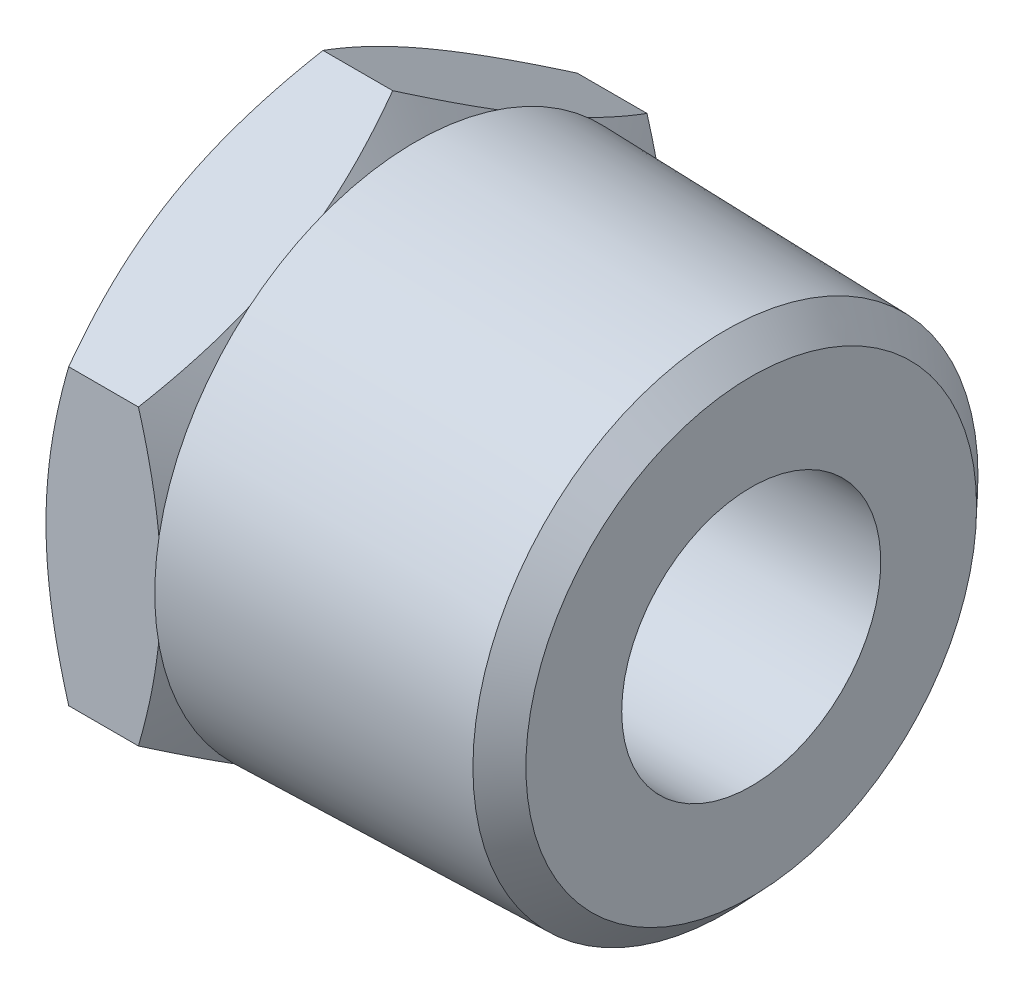
SolidWorks part; units mm, degrees
ref_plane "Front Plane" through (0, 0, 0) normal (0, 0, 1) x (1, 0, 0)
ref_plane "Top Plane" through (0, 0, 0) normal (0, 1, 0) x (1, 0, 0)
ref_plane "Right Plane" through (0, 0, 0) normal (1, 0, 0) x (0, 0, -1)
sketch "Sketch1" plane through (0, 0, 0) normal (0, 0, 1) x (1, 0, 0)
  line L0 (-11.938, 0) -> (11.938, 0) construction
  line L1 (-11.938, 13.462) -> (-11.938, -13.462) construction
  line L2 (11.938, 13.335) -> (11.938, -13.335) construction
  line L3 (-5.842, 6.858) -> (-5.842, -6.858) construction
  line L4 (11.938, -13.335) -> (-11.938, -13.9602) construction
  point P7 (-8.2169, 0)
  point P8 (-5.842, 0)
  point P11 (4.6809, -13.525)
  dimension "Male Pipe OD" = 26.67
  dimension "Hex" = 26.924
  dimension "Male TE" = 20.1549
  dimension "Female TE" = 6.096
  dimension "A" = 23.876
  dimension "Female Pipe OD" = 13.716
  dimension "D1" = 1.5
  dimension "D2" = 7.2571
ref_plane "Plane1" through (11.938, 0, 0) normal (1, 0, 0) x (0, 0, -1)
sketch "Sketch2" plane through (11.938, 0, 0) normal (1, 0, 0) x (0, 0, -1)
  circle A0 centre (0, 0) radius 13.335
extrude "Extrude1" add sketch "Sketch2" against normal up to vertex (17.78 mm away) draft 1.5 up to point (-5.842, 0, 0) draft outward yes
sketch "Sketch3" plane through (11.938, 0, 0) normal (1, 0, 0) x (0, 0, -1)
  circle A0 centre (0, 0) radius 13.335 construction
  circle A1 centre (0, 0) radius 13.335
curve "Helix/Spiral1" parameters "Male pitch"=1.8143
chamfer "Chamfer1" distance 1.3662 angle 45 1 edges at (11.938, 0, -13.335) first distance on face at (-5.842, 0, -13.8006)
sketch "Sketch4" plane through (0, 0, 0) normal (0, 0, 1) x (1, 0, 0)
  line L0 (11.1443, 13.335) -> (11.8246, 12.1566)
  line L1 (11.8246, 12.1566) -> (12.0514, 12.1566)
  line L2 (12.0514, 12.1566) -> (12.7317, 13.335)
  line L3 (11.1443, 13.335) -> (12.7317, 13.335) construction
  line L4 (11.938, 12.1566) -> (11.938, 13.335) construction
  line L5 (11.4844, 12.7458) -> (12.3916, 12.7458) construction
  line L6 (12.7317, 13.335) -> (10.9643, 13.6466)
  line L7 (11.1443, 13.335) -> (10.9643, 13.6466)
  dimension "D1" = 10
  dimension "D2" = 60
  dimension "D3" = 0.2268
  dimension "D4" = 0.9071
sweep "Cut-Sweep1" [suppressed] cut profiles "Sketch4" path "Helix/Spiral1"
sketch "Sketch5" plane through (-5.842, 0, 0) normal (-1, 0, 0) x (0, 0, 1)
  line L1 (0, 15.5446) -> (-13.462, 7.7723)
  line L2 (-13.462, 7.7723) -> (-13.462, -7.7723)
  line L3 (-13.462, -7.7723) -> (0, -15.5446)
  line L4 (0, -15.5446) -> (13.462, -7.7723)
  line L5 (13.462, -7.7723) -> (13.462, 7.7723)
  line L6 (13.462, 7.7723) -> (0, 15.5446)
  circle A0 centre (0, 0) radius 13.462 construction
  dimension "D1" = 26.924
extrude "Extrude2" add sketch "Sketch5" along normal up to vertex (6.096 mm away) up to point (-11.938, 0, 0)
ref_plane "Plane2" through (-5.842, 0, 0) normal (1, 0, 0) x (0, 0, -1)
sketch "Sketch6" plane through (-5.842, 0, 0) normal (1, 0, 0) x (0, 0, -1)
  circle A0 centre (0, 0) radius 6.858
extrude "Cut-Extrude1" cut sketch "Sketch6" against normal through all draft 1.5 draft outward yes
sketch "Sketch7" plane through (-5.842, 0, 0) normal (-1, 0, 0) x (0, 0, 1)
  circle A1 centre (0, 0) radius 6.858
  circle A2 centre (0, 0) radius 6.858
  dimension "D1" = 0
curve "Helix/Spiral2" parameters "Female Pitch"=1.4111
sketch "Sketch9" plane through (-11.938, 0, 0) normal (-1, 0, 0) x (0, 0, 1)
  circle A0 centre (0, 0) radius 7.0176 construction
  circle A1 centre (0, 0) radius 7.0176
sketch "Sketch8" plane through (0, 0, 0) normal (0, 0, 1) x (1, 0, 0)
  line L0 (-6.4594, 6.858) -> (-5.2246, 6.858) construction
  line L1 (-5.2246, 6.858) -> (-5.7538, 5.9415)
  line L2 (-5.7538, 5.9415) -> (-5.9302, 5.9415)
  line L3 (-5.9302, 5.9415) -> (-6.4594, 6.858)
  line L4 (-5.2246, 6.858) -> (-6.5993, 7.1004)
  line L5 (-6.4594, 6.858) -> (-6.5993, 7.1004)
  line L6 (-5.842, 5.9415) -> (-5.842, 6.858) construction
  line L7 (-6.1948, 6.3997) -> (-5.4892, 6.3997) construction
  dimension "D1" = 10
  dimension "D2" = 60
  dimension "D3" = 0.1764
  dimension "D4" = 0.7056
sweep "Sweep1" [suppressed] add profiles "Sketch8" path "Helix/Spiral2"
sketch "Sketch10" plane through (-11.938, 0, 0) normal (-1, 0, 0) x (0, 0, 1)
  line L3 (13.462, 7.7723) -> (0, 15.5446)
  line L4 (13.462, 7.7723) -> (0, 15.5446)
  line L5 (0, 15.5446) -> (-13.462, 7.7723)
  line L6 (0, 15.5446) -> (-13.462, 7.7723)
  line L10 (0, -15.5446) -> (13.462, -7.7723)
  line L11 (-13.462, 7.7723) -> (-13.462, -7.7723)
  line L12 (-13.462, 7.7723) -> (-13.462, -7.7723)
  line L13 (-13.462, -7.7723) -> (0, -15.5446)
  line L14 (-13.462, -7.7723) -> (0, -15.5446)
  line L15 (13.462, -7.7723) -> (13.462, 7.7723)
  line L16 (0, -15.5446) -> (13.462, -7.7723)
  line L17 (13.462, -7.7723) -> (13.462, 7.7723)
  dimension "D1" = 0
extrude "Cut-Extrude3" [suppressed] cut sketch "Sketch10" along normal through all
extrude "Cut-Extrude4" cut sketch "Sketch9" against normal through all draft 45
sketch "Sketch11" [suppressed] plane through (-5.842, 0, 0) normal (-1, 0, 0) x (0, 0, 1)
  circle A0 centre (0, 0) radius 5.9415
extrude "Cut-Extrude5" [suppressed] cut sketch "Sketch11" against normal through all
sketch "Sketch12" plane through (-11.938, 0, 0) normal (-1, 0, 0) x (0, 0, 1)
  circle A0 centre (0, 0) radius 13.462 construction
  circle A1 centre (0, 0) radius 13.462
extrude "Cut-Extrude6" cut sketch "Sketch12" against normal through all draft 60 flip side to cut
sketch "Sketch13" plane through (-5.842, 0, 0) normal (1, 0, 0) x (0, 0, -1)
  circle A1 centre (0, 0) radius 13.462
  circle A2 centre (0, 0) radius 13.462
  dimension "D1" = 0
extrude "Cut-Extrude7" cut sketch "Sketch13" against normal through all draft 60 flip side to cut
sketch "Sketch14" [suppressed] plane through (-11.938, 0, 0) normal (1, 0, 0) x (0, 0, -1)
  line L0 (0, 0) -> (4.2012, 4.2012) construction
  line L1 (0, 0) -> (5.9415, 0) construction
  circle A0 centre (0, 0) radius 5.9415 construction
  dimension "D1" = 45
sketch "Sketch15" plane through (-5.842, 0, 0) normal (-1, 0, 0) x (0, 0, 1)
  circle A1 centre (0, 0) radius 6.858
  circle A2 centre (0, 0) radius 6.858
  dimension "D1" = 0
extrude "Cut-Extrude8" cut sketch "Sketch15" against normal through all
equation "\"D3@Sketch4\" = \"Male pitch@Helix/Spiral1\"*.125"
equation "\"D4@Sketch4\" = \"Male pitch@Helix/Spiral1\"*.50"
equation "\"D1@Chamfer1\" = \"Male pitch@Helix/Spiral1\"*.753"
equation "\"D1@Sketch5\" = \"Hex@Sketch1\""
equation "\"D3@Sketch8\" = \"Female Pitch@Helix/Spiral2\"*.125"
equation "\"D4@Sketch8\" = \"Female Pitch@Helix/Spiral2\"*.5"
equation "\"D2@Sketch1\" = \"Male pitch@Helix/Spiral1\"*4.0"
